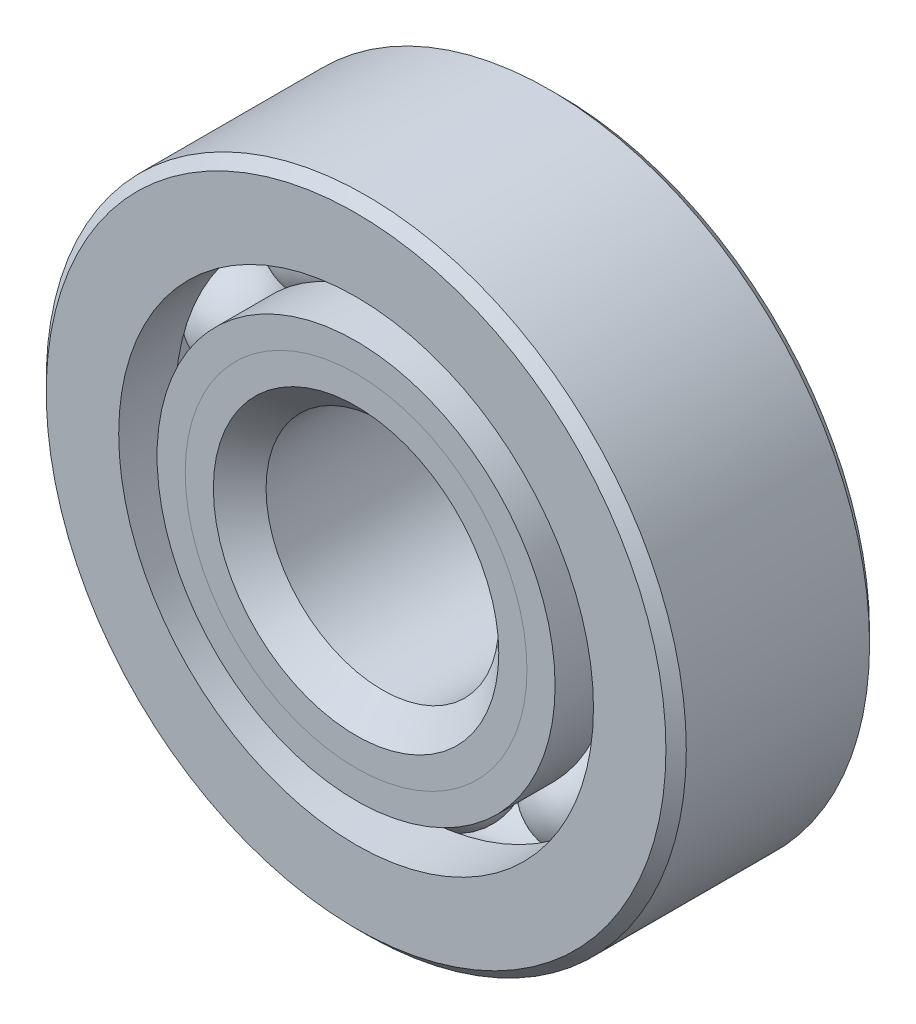
SolidWorks part; units mm, degrees
ref_plane "Front Plane" through (0, 0, 0) normal (0, 0, 1) x (1, 0, 0)
ref_plane "Top Plane" through (0, 0, 0) normal (0, 1, 0) x (1, 0, 0)
ref_plane "Right Plane" through (0, 0, 0) normal (1, 0, 0) x (0, 0, -1)
sketch "Sketch1" plane through (0, 0, 0) normal (1, 0, 0) x (0, 0, -1)
  line L0 (-3.5, 0) -> (3.5, 0) construction
  line L1 (0, 11) -> (0, -11) construction
  line L2 (3.15, 11) -> (-3.15, 11)
  line L3 (-3.15, 11) -> (-3.5, 10.65)
  line L4 (-3.5, 10.65) -> (-3.5, 8.1593)
  line L5 (-3.5, 8.1593) -> (-1.5556, 8.1593)
  line L6 (3.5, 8.1593) -> (1.5556, 8.1593)
  line L7 (3.5, 10.65) -> (3.5, 8.1593)
  line L8 (3.15, 11) -> (3.5, 10.65)
  line L9 (0, 11) -> (0, 7.5) construction
  line L10 (0, 7.5) -> (0, 4) construction
  arc A0 (-1.5556, 8.1593) -> (1.5556, 8.1593) centre (0, 7.5) cw
  point P14 (0, 4)
  dimension "D3" = 3.1111
  dimension "D1" = 45
  dimension "Width" = 7
  dimension "OD" = 22
  dimension "D2" = 0.35
  dimension "Shaft Dia" = 8
  dimension "D4" = 0.6593
revolve "Revolve1" add sketch "Sketch1" angle 360 about L0
sketch "Sketch2" plane through (0, 0, 0) normal (1, 0, 0) x (0, 0, -1)
  line L0 (-3.5, 6.8407) -> (-1.5556, 6.8407)
  line L1 (-3.5, 10.65) -> (-3.5, -10.65) construction
  line L2 (-3.5, 6.8407) -> (-3.5, 5.8729)
  line L3 (-3.5, 5.8729) -> (-2.5323, 4.9052)
  line L4 (-2.5323, 4.9052) -> (0, 4.9052)
  line L5 (0, 11) -> (0, -11) construction
  line L6 (0, 4.9052) -> (0, 5.8105)
  line L7 (0, 5.8105) -> (0, 4) construction
  line L8 (-3.5, 6.8407) -> (-3.5, 4.9052) construction
  line L9 (-3.5, 4.9052) -> (-2.5323, 4.9052) construction
  arc A0 (-1.5556, 6.8407) -> (0, 5.8105) centre (0, 7.5) ccw
  arc A1 (1.5556, 8.1593) -> (-1.5556, 8.1593) centre (0, 7.5) ccw construction
  circle A2 centre (0, 7.5) radius 1.6895 construction
  dimension "D1" = 45
revolve "Revolve2" add sketch "Sketch2" angle 360 about L0
sketch "Sketch3" plane through (0, 0, 0) normal (1, 0, 0) x (0, 0, -1)
  line L0 (-3.5, 5.8729) -> (-2.5323, 4.9052)
  line L1 (-2.5323, 4.9052) -> (0, 4.9052)
  line L2 (0, 4.9052) -> (0, 5.8105)
  line L3 (-3.5, 5.8729) -> (-3.5, 4.9052)
  line L4 (-3.5, 6.8407) -> (-3.5, 4.9052) construction
  line L5 (-3.5, 4.9052) -> (-2.5948, 4)
  line L6 (-2.5948, 4) -> (3.15, 4)
  line L7 (3.15, 11) -> (3.15, -11) construction
  line L8 (3.15, 4) -> (3.5, 4.35)
  line L9 (3.5, -10.65) -> (3.5, 10.65) construction
  line L10 (3.5, 4.35) -> (3.5, 6.8407)
  line L11 (3.5, 6.8407) -> (1.5556, 6.8407)
  line L13 (3.15, 11) -> (3.5, 10.65) construction
  circle A0 centre (0, 7.5) radius 1.6895 construction
  arc A1 (1.5556, 6.8407) -> (0, 5.8105) centre (0, 7.5) cw
revolve "Revolve3" add sketch "Sketch3" angle 360 about L0
sketch "Sketch4" plane through (0, 0, 0) normal (1, 0, 0) x (0, 0, -1)
  line L0 (-1.6895, 7.5) -> (1.6895, 7.5)
  circle A1 centre (0, 7.5) radius 1.6895 construction
  arc A2 (-1.6895, 7.5) -> (1.6895, 7.5) centre (0, 7.5) cw
  arc A3 (1.5556, 8.1593) -> (-1.5556, 8.1593) centre (0, 7.5) ccw construction
revolve "Revolve4" add sketch "Sketch4" angle 360 about L0
ref_axis "Axis1" through (0, 0, -3.5) along (0, 0, 1)
pattern_circular "CirPattern1" count 10 every 36 about axis through (0, 0, -3.5) along (0, 0, 1) of bodies 104
equation "\"D2@Sketch1\" = \"Width@Sketch1\"*.05"
equation "\"D3@Sketch1\" = \"Width@Sketch1\"/2.25"
equation "\"D4@Sketch1\" = (((\"OD@Sketch1\"-\"Width@Sketch1\")/2)/3.25)/3.5"
equation "\"D2@CirPattern1\" = 360/\"Balls@CirPattern1\""
